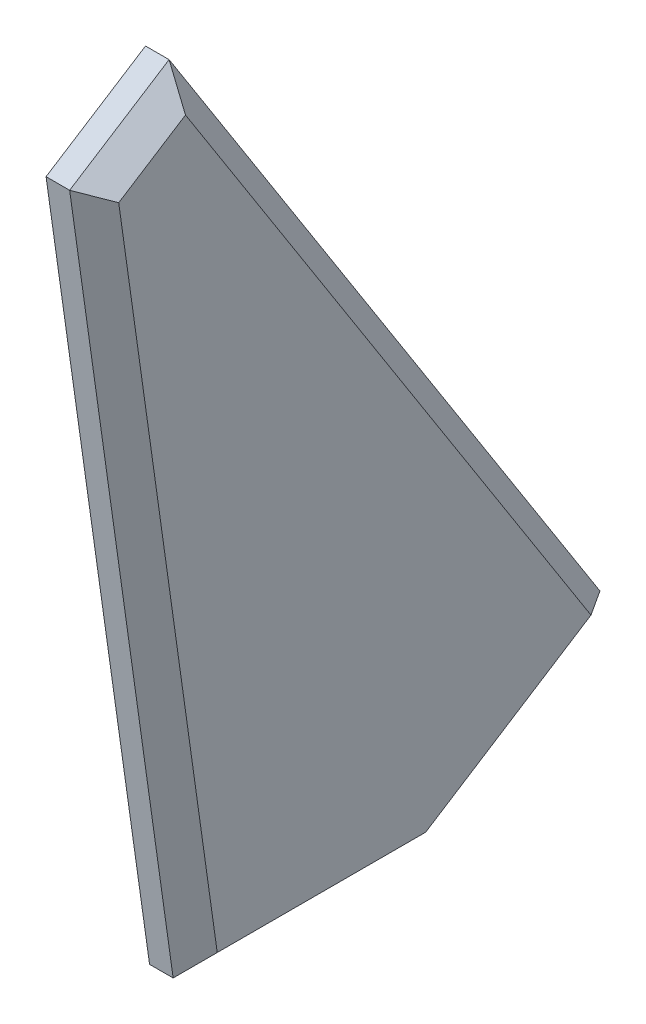
SolidWorks part; units mm, degrees
ref_plane "前视基准面" through (0, 0, 0) normal (0, 0, 1) x (1, 0, 0)
ref_plane "上视基准面" through (0, 0, 0) normal (0, 1, 0) x (1, 0, 0)
ref_plane "右视基准面" through (0, 0, 0) normal (1, 0, 0) x (0, 0, -1)
other "Configuration Table"
sketch "草图1" plane through (0, 0, 0) normal (1, 0, 0) x (0, 0, -1)
  line L0 (0, 0) -> (-49.9898, 0)
  line L1 (-49.9898, 0) -> (-71.9271, 155.5608)
  line L2 (-71.9271, 155.5608) -> (-50.8486, 169.0032)
  line L3 (-50.8486, 169.0032) -> (40.4707, 25.8094)
  line L4 (40.4707, 25.8094) -> (0, 0)
  dimension "D1" = 48
  dimension "D2" = 49.5
  dimension "D3" = 157.1
  dimension "D4" = 25
  dimension "D5" = 114.5
extrude "凸台-拉伸1" add sketch "草图1" along normal blind 5
sketch "草图2" plane through (5, 0, 0) normal (1, 0, 0) x (0, 0, -1)
  line L5 (0, 0) -> (40.4707, 25.8094)
  line L6 (40.4707, 25.8094) -> (-50.8486, 169.0032)
  line L7 (-50.8486, 169.0032) -> (-71.9271, 155.5608)
  line L8 (-71.9271, 155.5608) -> (-49.9898, 0)
  line L9 (-49.9898, 0) -> (0, 0)
  line L10 (0, 0) -> (40.4707, 25.8094)
  line L11 (40.4707, 25.8094) -> (-50.8486, 169.0032)
  line L12 (-50.8486, 169.0032) -> (-71.9271, 155.5608)
  line L13 (-71.9271, 155.5608) -> (-49.9898, 0)
  line L14 (-49.9898, 0) -> (0, 0)
  dimension "D1" = 0
extrude "凸台-拉伸2" add sketch "草图2" along normal blind 5 separate body
chamfer "倒角1" distance 5 angle 45 5 edges at (10, 77.7804, 60.9584) (10, 162.282, 61.3878) (10, 97.4063, 5.189) (10, 12.9047, -20.2353) (10, 0, 24.9949)
